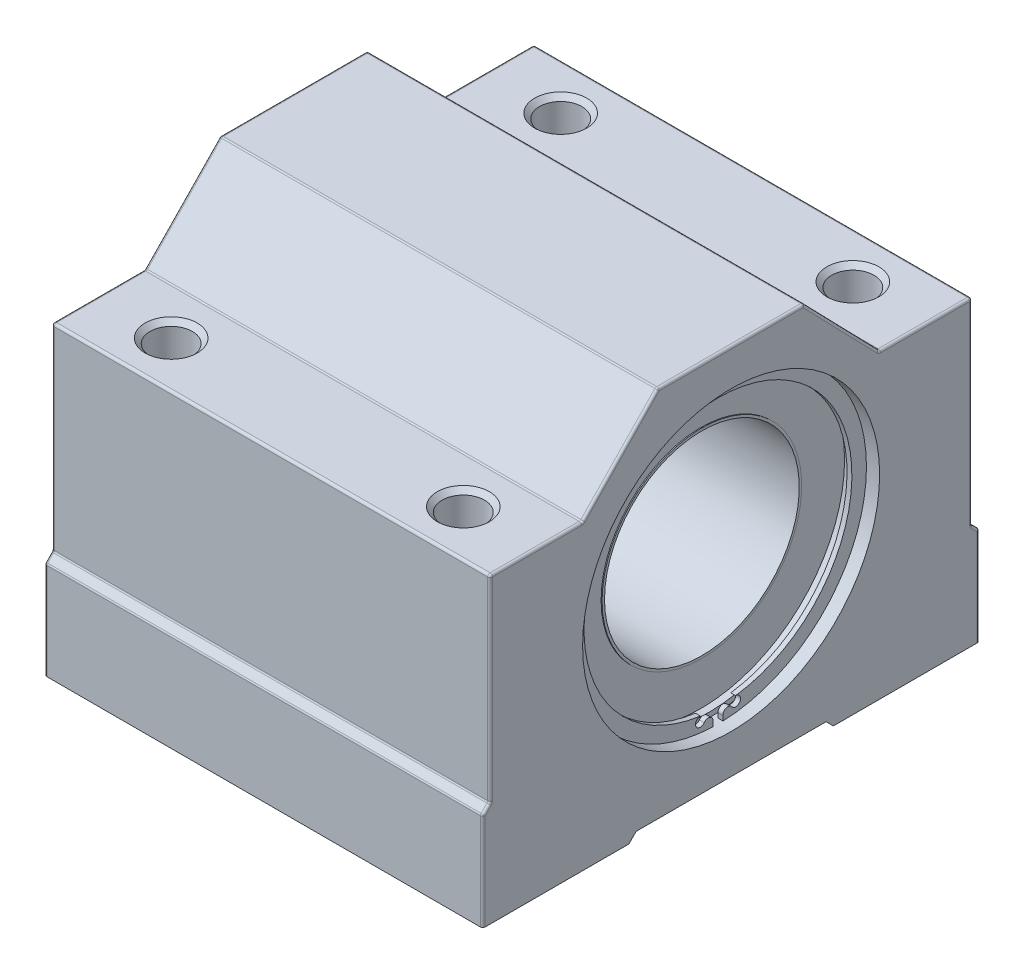
SolidWorks part; units mm, degrees
ref_plane "Front Plane" through (0, 0, 0) normal (0, 0, 1) x (1, 0, 0)
ref_plane "Top Plane" through (0, 0, 0) normal (0, 1, 0) x (1, 0, 0)
ref_plane "Right Plane" through (0, 0, 0) normal (1, 0, 0) x (0, 0, -1)
sketch "Sketch1" plane through (0, 0, 0) normal (1, 0, 0) x (0, 0, -1)
  line L1 (-21, -40) -> (-19.5, -38.5)
  line L2 (-19.5, -38.5) -> (19.5, -38.5)
  line L3 (19.5, -38.5) -> (21, -40)
  line L4 (21, -40) -> (51, -40)
  line L6 (51, -20) -> (49.5, -18.5)
  line L8 (49.5, 22) -> (30.5, 22)
  line L9 (30.5, 22) -> (15, 38)
  line L10 (15, 38) -> (-15, 38)
  line L11 (-15, 38) -> (-30.5, 22)
  line L12 (-30.5, 22) -> (-49.5, 22)
  line L15 (-51, -20) -> (-51, -40)
  line L16 (0, -38.5) -> (0, 38) construction
  line L17 (-16.278, 0) -> (14.0247, 0) construction
  line L18 (-51, -40) -> (-21, -40)
  line L19 (51, -20) -> (51, -40)
  line L20 (-49.5, -18.5) -> (-49.5, 22)
  line L21 (49.5, -18.5) -> (49.5, 22)
  line L22 (-40, 22) -> (-40, -40) construction
  line L23 (-40, -40) -> (40, 22) construction
  line L24 (40, 22) -> (40, -40) construction
  line L25 (-51, -20) -> (-49.5, -18.5)
  line L26 (-30.5, 0) -> (30.5, 0) construction
  circle A0 centre (0, 0) radius 30.5
  circle A1 centre (0, 0) radius 29.5
  circle A2 centre (0, 0) radius 20
  point P18 (0, 38)
  dimension "D12" = 40
  dimension "D1" = 102
  dimension "D2" = 62
  dimension "D3" = 40
  dimension "D5" = 78
  dimension "D6" = 80
  dimension "D4" = 20
  dimension "D7" = 1.5
  dimension "D8" = 30
  dimension "D9" = 1.5
  dimension "D10" = 30
  dimension "D11" = 1
extrude "Boss-Extrude1" add sketch "Sketch1" along normal blind 90 contours L25 L15 L18 L1 L2 L3 L4 L19 L6 L21 L8 L9 L10 L11 L12 L20 A0 region at (0, -38.7159, 36)
extrude "Extrude-Thin1" add sketch "Sketch1<4>" along normal blind 83.5 from offset 0.5 separate body thin contours A2 thin type one direction wall 0.5
sketch "Sketch1<4>" plane through (0, 0, 0) normal (1, 0, 0) x (0, 0, -1) same geometry as "Sketch1"
extrude "Boss-Extrude2" add sketch "Sketch1<5>" along normal blind 83 from offset 0.8 contours A1 A2 region at (0, 0, 28.6656)
sketch "Sketch1<5>" plane through (0, 0, 0) normal (1, 0, 0) x (0, 0, -1) same geometry as "Sketch1"
extrude "Boss-Extrude3" add sketch "Sketch1<6>" along normal blind 85 from offset 0.3 contours A0 A1 region at (0, 0, 29.6373)
sketch "Sketch1<6>" plane through (0, 0, 0) normal (1, 0, 0) x (0, 0, -1) same geometry as "Sketch1"
ref_plane "Plane1" through (85.3, 0, 0) normal (1, 0, 0) x (0, 0, -1)
sketch "Sketch3" plane through (85.3, 0, 0) normal (1, 0, 0) x (0, 0, -1)
  line L0 (0, 0) -> (0, -50000) construction
  line L1 (-1.0013, -29.483) -> (-1.0352, -30.4824)
  line L2 (1.0013, -29.483) -> (1.0352, -30.4824)
  circle A0 centre (0, 0) radius 30.5 construction
  arc A1 (1.0352, -30.4824) -> (-1.0352, -30.4824) centre (0, 0) ccw
  circle A2 centre (0, 0) radius 29.5 construction
  arc A3 (0, -29.5) -> (1.0013, -29.483) centre (0, 0) ccw
  arc A4 (-1.0013, -29.483) -> (-2.8133, -28.8502) centre (-2, -29.4321) ccw
  circle A5 centre (-2, -29.4321) radius 0.25
  arc A6 (-2.2494, -29.4141) -> (-1.7505, -29.448) centre (0, 0) ccw
  arc A7 (-2.8133, -28.8502) -> (-3.6214, -27.2683) centre (-3.6265, -28.2683) cw
  arc A8 (2.8133, -28.8502) -> (3.6214, -27.2683) centre (3.6265, -28.2683) ccw
  circle A10 centre (2, -29.4321) radius 0.25
  arc A11 (1.0013, -29.483) -> (2.8133, -28.8502) centre (2, -29.4321) cw
  arc A13 (3.6214, -27.2683) -> (-3.6214, -27.2683) centre (0, 0) ccw
  dimension "D1" = 0.5
  dimension "D2" = 2
  dimension "D3" = 1
  dimension "D4" = 2
extrude "Boss-Extrude4" add sketch "Sketch3" along normal blind 1 from offset 1 contours A11 A8 A13 A7 A4 L1 A1 L2
fillet "Fillet1" radius 0.5 32 edges at (45, -18.5, -49.5) (45, -18.5, 49.5) (45, -20, 51) (45, -20, -51) (45, 22, -30.5) (45, 22, 30.5) (45, 38, 15) (45, 38, -15) (45, 22, -49.5) (45, 22, 49.5) (90, 30, -22.75) (90, 30, 22.75) (90, 1.75, 49.5) (0, -19.25, 50.25) (0, 30, 22.75) (90, -19.25, -50.25) (90, -30, -51) (90, 1.75, -49.5) (90, 38, 0) (90, 22, -40) (90, 22, 40) (90, -19.25, 50.25) (90, -30, 51) (0, -30, -51) (0, -19.25, -50.25) (0, 1.75, -49.5) (0, 30, -22.75) (0, 22, -40) (0, 38, 0) (0, -30, 51) (0, 1.75, 49.5) (0, 22, 40)
sketch "Sketch4" plane through (0, -40, 0) normal (0, -1, 0) x (1, 0, 0)
  line L0 (45, 51) -> (45, -51) construction
  line L1 (89.5, 51) -> (0.5, 51) construction
  line L2 (89.5, -51) -> (0.5, -51) construction
  line L4 (-4.9444, 40) -> (27.0918, 40) construction
  line L6 (0, 0) -> (36.1646, 0) construction
  circle A0 centre (15, 40) radius 4.35
  circle A1 centre (75, 40) radius 4.35
  circle A2 centre (75, -40) radius 4.35
  circle A3 centre (15, -40) radius 4.35
  dimension "D2" = 8.7
  dimension "D1" = 40
  dimension "D3" = 60
extrude "Cut-Extrude3" cut sketch "Sketch4" against normal through all
chamfer "Chamfer1" distance 1 angle 45 6 edges at (75, 22, -44.35) (15, 22, -44.35) (15, 22, 35.65) (75, 22, 35.65) (75, -40, 44.35) (15, -40, 35.65)
equation "\"D1@Boss-Extrude2\"= \"D1@Boss-Extrude1\" - 2 - 5"
equation "\"D1@Boss-Extrude3\"= \"D1@Boss-Extrude1\" - 5"
equation "\"D1@Sketch4\"= \"D6@Sketch1\" / 2"
equation "\"D1@Extrude-Thin1\"= \"D1@Boss-Extrude3\" - 1.5"
